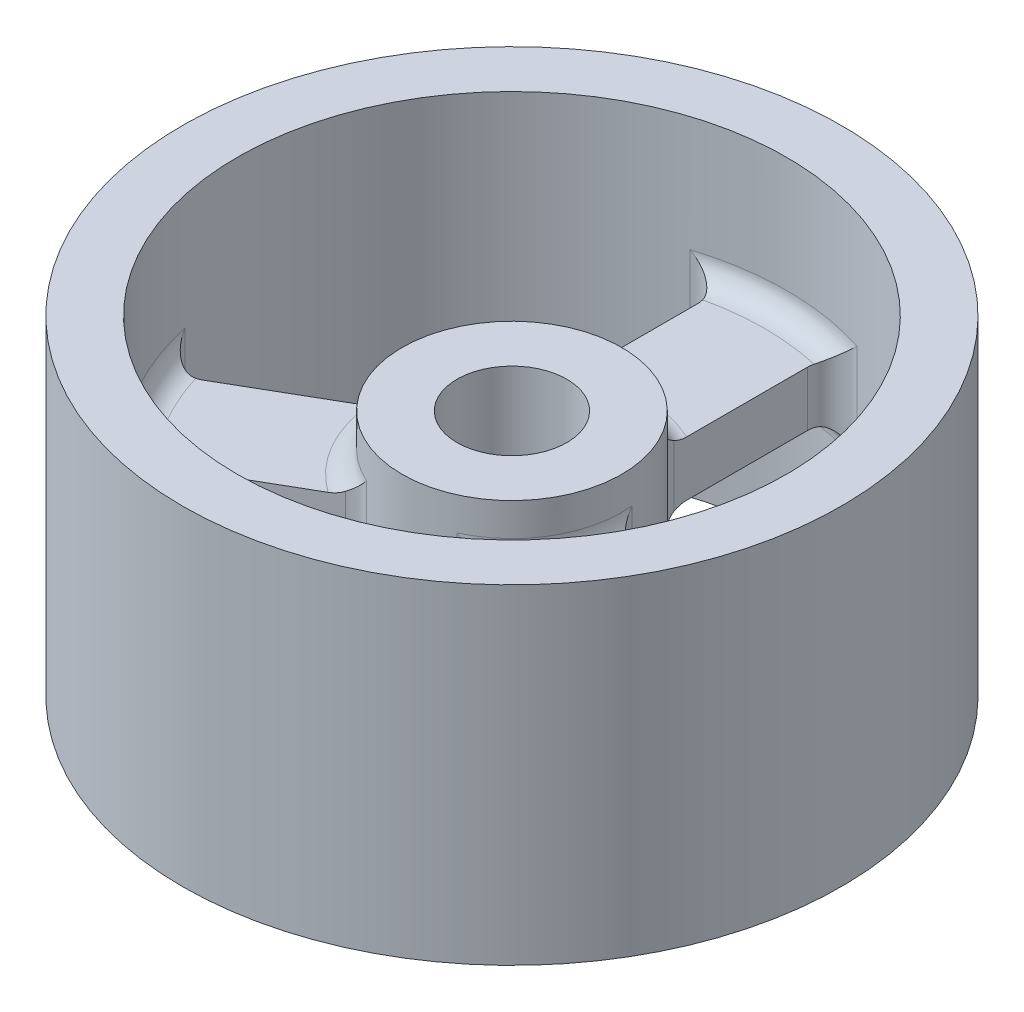
SolidWorks part; units mm, degrees
ref_plane "Front Plane" through (0, 0, 0) normal (0, 0, 1) x (1, 0, 0)
ref_plane "Top Plane" through (0, 0, 0) normal (0, 1, 0) x (1, 0, 0)
ref_plane "Right Plane" through (0, 0, 0) normal (1, 0, 0) x (0, 0, -1)
sketch "Sketch1" plane through (0, 0, 0) normal (0, 1, 0) x (1, 0, 0)
  line L0 (5, 9.7468) -> (5, 21.9089)
  line L1 (0, 30) -> (0, -30) construction
  line L2 (-5, 9.7468) -> (-5, 21.9089)
  line L3 (5.941, -9.2035) -> (16.4737, -15.2846)
  line L4 (10.941, -0.5433) -> (21.4737, -6.6243)
  line L5 (-10.941, -0.5433) -> (-21.4737, -6.6243)
  line L6 (-5.941, -9.2035) -> (-16.4737, -15.2846)
  circle A0 centre (0, 0) radius 30
  circle A1 centre (0, 0) radius 25
  circle A2 centre (0, 0) radius 10
  circle A3 centre (0, 0) radius 5
  arc A4 (5, 9.7468) -> (5.8333, 8.1223) centre (7, 9.7468) ccw
  arc A5 (-5, 9.7468) -> (-5.8333, 8.1223) centre (-7, 9.7468) cw
  arc A6 (7.6087, 23.814) -> (5, 21.9089) centre (7, 21.9089) ccw
  arc A7 (-7.6087, 23.814) -> (-5, 21.9089) centre (-7, 21.9089) cw
  arc A8 (16.8192, -18.4963) -> (16.4737, -15.2846) centre (15.4737, -17.0166) ccw
  arc A9 (24.4279, -5.3177) -> (21.4737, -6.6243) centre (22.4737, -4.8923) cw
  arc A10 (10.941, -0.5433) -> (9.9508, 0.9907) centre (11.941, 1.1888) cw
  arc A11 (5.941, -9.2035) -> (4.1175, -9.113) centre (4.941, -10.9356) ccw
  arc A12 (-24.4279, -5.3177) -> (-21.4737, -6.6243) centre (-22.4737, -4.8923) ccw
  arc A13 (-16.8192, -18.4963) -> (-16.4737, -15.2846) centre (-15.4737, -17.0166) cw
  arc A14 (-5.941, -9.2035) -> (-4.1175, -9.113) centre (-4.941, -10.9356) cw
  arc A15 (-10.941, -0.5433) -> (-9.9508, 0.9907) centre (-11.941, 1.1888) ccw
  point P47 (0, 0)
  dimension "D1" = 60
  dimension "D2" = 50
  dimension "D4" = 20
  dimension "D5" = 10
  dimension "D6" = 4
  dimension "D7" = 4
  dimension "D3" = 5
  dimension "D8" = 3
extrude "Boss-Extrude1" add sketch "Sketch1" along normal mid plane 5 contours A1 L1 A2 A4 L0 A6 | L1 A1 A7 L2 A5 A2 | A15 L5 A12 A1 A13 L6 A14 A2 | A11 L3 A8 A1 A9 L4 A10 A2 region at (2.5908, 0, -17.3093) region at (14.9903, 0, 8.6546) region at (-2.5908, 0, -17.3093) region at (-14.9903, 0, 8.6546)
extrude "Boss-Extrude2" add sketch "Sketch1<4>" along normal mid plane 15 contours A2 L1 A3 | L1 A2 A3 region at (8.4666, 0, -4.8882) region at (-0.2236, 0, -7.5)
sketch "Sketch1<4>" plane through (0, 0, 0) normal (0, 1, 0) x (1, 0, 0) same geometry as "Sketch1"
extrude "Boss-Extrude3" add sketch "Sketch1<5>" along normal mid plane 30 contours A0 L1 A1 | L1 A0 A1 region at (3.9536, 0, -25.3645) region at (-3.9536, 0, -25.3645)
sketch "Sketch1<5>" plane through (0, 0, 0) normal (0, 1, 0) x (1, 0, 0) same geometry as "Sketch1"
fillet "Fillet1" radius 2 6 edges at (21.6506, 2.5, 12.5) (0, 2.5, -25) (-21.6506, 2.5, 12.5) (21.6506, -2.5, 12.5) (-21.6506, -2.5, 12.5) (0, -2.5, -25)
fillet "Fillet2" radius 2 6 edges at (0, -2.5, -10) (-8.6603, -2.5, 5) (8.6603, -2.5, 5) (-8.6603, 2.5, 5) (8.6603, 2.5, 5) (0, 2.5, -10)
